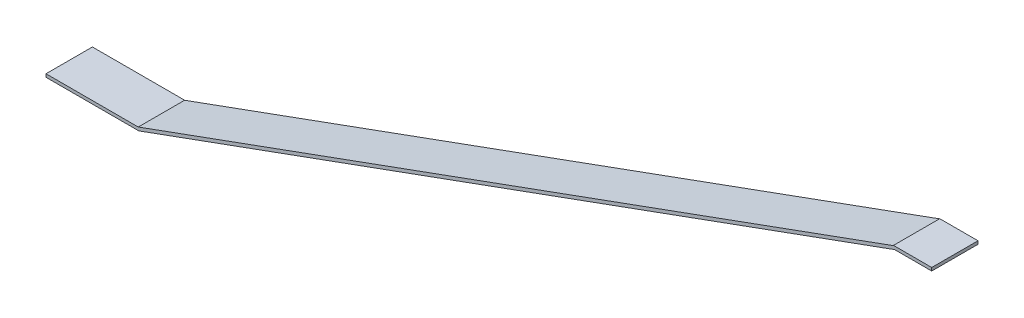
SolidWorks part; units mm, degrees
ref_plane "Front Plane" through (0, 0, 0) normal (0, 0, 1) x (1, 0, 0)
ref_plane "Top Plane" through (0, 0, 0) normal (0, 1, 0) x (1, 0, 0)
ref_plane "Right Plane" through (0, 0, 0) normal (1, 0, 0) x (0, 0, -1)
ref_axis "Axis1" through (0, -2, 0) along (0, 1, 0)
sketch "Sketch2" plane through (0, 0, 0) normal (0, 1, 0) x (1, 0, 0)
  line L1 (0, 0) -> (30, 0)
  line L2 (0, 0) -> (0, 15)
  line L3 (0, 15) -> (30, 15)
  line L4 (30, 0) -> (30, 15)
  dimension "D1" = 30
extrude "Boss-Extrude1" add sketch "Sketch2" along normal blind 1 contours L2 L1 L4 L3
ref_plane "Plane1" through (3.5093, -9.6418, 0) normal (0.342, -0.9397, 0) x (0, 0, -1)
sketch "Sketch4" plane through (3.5093, -9.6418, 0) normal (0.342, -0.9397, 0) x (0, 0, -1)
  line L0 (0, 0.55) -> (0, -0.55) construction
  line L1 (0, 28.1908) -> (14.9804, 28.1908)
  line L2 (0, 28.1908) -> (0, 288.1908)
  line L3 (0, 288.1908) -> (14.9804, 288.1908)
  line L4 (14.9804, 28.1908) -> (14.9804, 288.1908)
  line L5 (0, 28.1908) -> (15, 28.1908) construction
  dimension "D1" = 260
extrude "Boss-Extrude2" add sketch "Sketch4" against normal blind 1
ref_plane "Plane2" through (274.3201, 0, 0) normal (1, 0, 0) x (0, 0, 1)
sketch "Sketch6" plane through (274.3201, 0, 0) normal (1, 0, 0) x (0, 0, 1)
  line L1 (0, -88.9252) -> (-14.9584, -88.9252)
  line L2 (0, -88.9252) -> (0, -89.9252)
  line L3 (0, -89.9252) -> (-14.9584, -89.9252)
  line L4 (-14.9584, -88.9252) -> (-14.9584, -89.9252)
  point P4 (0, -88.9252)
  point P5 (0, 0)
extrude "Boss-Extrude3" add sketch "Sketch6" along normal blind 12 and the other way up to surface contours L2 L1 L4 L3 other way up to face at (274.1491, 89.3951, -7.4902)
